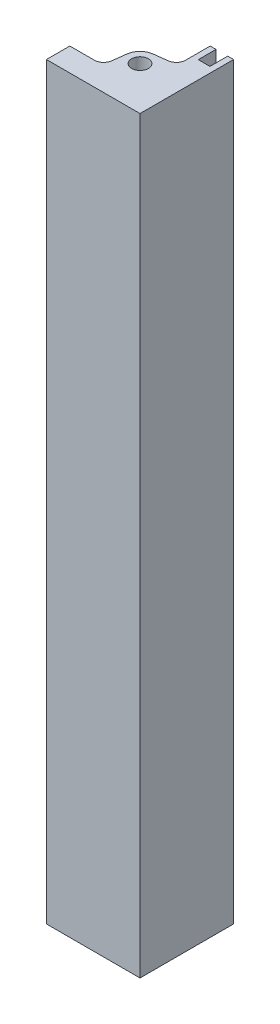
SolidWorks part; units mm, degrees
ref_plane "Front Plane" through (0, 0, 0) normal (0, 0, 1) x (1, 0, 0)
ref_plane "Top Plane" through (0, 0, 0) normal (0, 1, 0) x (1, 0, 0)
ref_plane "Right Plane" through (0, 0, 0) normal (1, 0, 0) x (0, 0, -1)
sketch "Sketch1" plane through (0, 0, 0) normal (0, 1, 0) x (1, 0, 0)
  line L0 (0, 0) -> (25.4, 0)
  line L1 (25.4, 0) -> (25.4, 25.4)
  line L2 (25.4, 25.4) -> (19.05, 25.4)
  line L3 (19.05, 25.4) -> (19.05, 6.35)
  line L4 (19.05, 6.35) -> (0, 6.35)
  line L5 (0, 6.35) -> (0, 0)
  dimension "D1" = 25.4
  dimension "D2" = 6.35
extrude "Boss-Extrude1" add sketch "Sketch1" along normal blind 203.2
sketch "Sketch2" plane through (0, 203.2, 0) normal (0, 1, 0) x (1, 0, 0)
  line L0 (19.05, 25.4) -> (19.05, 6.35) construction
  line L1 (19.05, 6.35) -> (0, 6.35) construction
  line L2 (19.05, 16.51) -> (19.05, 6.35)
  line L3 (19.05, 6.35) -> (8.89, 6.35)
  line L4 (8.89, 6.35) -> (9.6295, 12.244)
  line L5 (19.05, 16.51) -> (13.156, 15.7705)
  line L6 (13.6618, 11.7382) -> (19.05, 6.35) construction
  arc A0 (13.156, 15.7705) -> (9.6295, 12.244) centre (13.6618, 11.7382) ccw
  circle A1 centre (13.6618, 11.7382) radius 2.286
  dimension "D4" = 4.572
  dimension "D5" = 1.778
  dimension "D1" = 45
  dimension "D2" = 10.16
  dimension "D3" = 10.16
  dimension "D6" = 7.62
extrude "Boss-Extrude2" add sketch "Sketch2" against normal blind 6.35
ref_plane "Plane1" through (0, 101.6, 0) normal (0, 1, 0) x (1, 0, 0)
fillet "Fillet1" radius 2.54 2 edges at (19.05, 200.025, -16.51) (8.89, 200.025, -6.35)
mirror "Mirror1" about plane through (0, 101.6, 0) normal (0, 1, 0) of "Fillet1", "Boss-Extrude2"
sketch "Sketch4" plane through (0, 0, 0) normal (0, -1, 0) x (1, 0, 0)
  line L0 (25.4, -25.4) -> (19.05, -25.4) construction
  line L1 (20.6375, -25.4) -> (23.8125, -25.4)
  line L2 (20.6375, -25.4) -> (20.6375, -20.574)
  line L3 (20.6375, -20.574) -> (23.8125, -20.574)
  line L4 (23.8125, -25.4) -> (23.8125, -20.574)
  point P6 (22.225, -25.4)
  point P7 (22.225, -25.4)
  dimension "D1" = 3.175
  dimension "D2" = 4.826
extrude "Cut-Extrude2" cut sketch "Sketch4" against normal through all
sketch "Sketch5" plane through (19.05, 0, 0) normal (-1, 0, 0) x (0, 0, 1)
  line L0 (-25.4, 203.2) -> (-25.4, 0) construction
  line L1 (-25.4, 190.5) -> (-6.35, 190.5)
  line L2 (-25.4, 190.5) -> (-25.4, 185.674)
  line L3 (-25.4, 185.674) -> (-6.35, 185.674)
  line L4 (-6.35, 190.5) -> (-6.35, 185.674)
  line L5 (-6.35, 196.85) -> (-6.35, 6.35) construction
  line L6 (-18.7512, 196.85) -> (-16.231, 196.85) construction
  line L7 (-25.4, 180.8903) -> (-25.4, 176.0643)
  line L8 (-25.4, 180.8903) -> (-6.35, 180.8903)
  line L9 (-6.35, 180.8903) -> (-6.35, 176.0643)
  line L10 (-25.4, 176.0643) -> (-6.35, 176.0643)
  line L11 (-25.4, 171.2807) -> (-25.4, 166.4547)
  line L12 (-25.4, 171.2807) -> (-6.35, 171.2807)
  line L13 (-6.35, 171.2807) -> (-6.35, 166.4547)
  line L14 (-25.4, 166.4547) -> (-6.35, 166.4547)
  line L15 (-25.4, 161.671) -> (-25.4, 156.845)
  line L16 (-25.4, 161.671) -> (-6.35, 161.671)
  line L17 (-6.35, 161.671) -> (-6.35, 156.845)
  line L18 (-25.4, 156.845) -> (-6.35, 156.845)
  line L19 (-25.4, 152.0613) -> (-25.4, 147.2353)
  line L20 (-25.4, 152.0613) -> (-6.35, 152.0613)
  line L21 (-6.35, 152.0613) -> (-6.35, 147.2353)
  line L22 (-25.4, 147.2353) -> (-6.35, 147.2353)
  line L23 (-25.4, 142.4517) -> (-25.4, 137.6257)
  line L24 (-25.4, 142.4517) -> (-6.35, 142.4517)
  line L25 (-6.35, 142.4517) -> (-6.35, 137.6257)
  line L26 (-25.4, 137.6257) -> (-6.35, 137.6257)
  line L27 (-25.4, 132.842) -> (-25.4, 128.016)
  line L28 (-25.4, 132.842) -> (-6.35, 132.842)
  line L29 (-6.35, 132.842) -> (-6.35, 128.016)
  line L30 (-25.4, 128.016) -> (-6.35, 128.016)
  line L31 (-25.4, 123.2323) -> (-25.4, 118.4063)
  line L32 (-25.4, 123.2323) -> (-6.35, 123.2323)
  line L33 (-6.35, 123.2323) -> (-6.35, 118.4063)
  line L34 (-25.4, 118.4063) -> (-6.35, 118.4063)
  line L35 (-25.4, 113.6227) -> (-25.4, 108.7967)
  line L36 (-25.4, 113.6227) -> (-6.35, 113.6227)
  line L37 (-6.35, 113.6227) -> (-6.35, 108.7967)
  line L38 (-25.4, 108.7967) -> (-6.35, 108.7967)
  line L39 (-25.4, 104.013) -> (-25.4, 99.187)
  line L40 (-25.4, 104.013) -> (-6.35, 104.013)
  line L41 (-6.35, 104.013) -> (-6.35, 99.187)
  line L42 (-25.4, 99.187) -> (-6.35, 99.187)
  line L43 (-25.4, 94.4033) -> (-25.4, 89.5773)
  line L44 (-25.4, 94.4033) -> (-6.35, 94.4033)
  line L45 (-6.35, 94.4033) -> (-6.35, 89.5773)
  line L46 (-25.4, 89.5773) -> (-6.35, 89.5773)
  line L47 (-25.4, 84.7937) -> (-25.4, 79.9677)
  line L48 (-25.4, 84.7937) -> (-6.35, 84.7937)
  line L49 (-6.35, 84.7937) -> (-6.35, 79.9677)
  line L50 (-25.4, 79.9677) -> (-6.35, 79.9677)
  line L51 (-25.4, 75.184) -> (-25.4, 70.358)
  line L52 (-25.4, 75.184) -> (-6.35, 75.184)
  line L53 (-6.35, 75.184) -> (-6.35, 70.358)
  line L54 (-25.4, 70.358) -> (-6.35, 70.358)
  line L55 (-25.4, 65.5743) -> (-25.4, 60.7483)
  line L56 (-25.4, 65.5743) -> (-6.35, 65.5743)
  line L57 (-6.35, 65.5743) -> (-6.35, 60.7483)
  line L58 (-25.4, 60.7483) -> (-6.35, 60.7483)
  line L59 (-25.4, 55.9647) -> (-25.4, 51.1387)
  line L60 (-25.4, 55.9647) -> (-6.35, 55.9647)
  line L61 (-6.35, 55.9647) -> (-6.35, 51.1387)
  line L62 (-25.4, 51.1387) -> (-6.35, 51.1387)
  line L63 (-25.4, 46.355) -> (-25.4, 41.529)
  line L64 (-25.4, 46.355) -> (-6.35, 46.355)
  line L65 (-6.35, 46.355) -> (-6.35, 41.529)
  line L66 (-25.4, 41.529) -> (-6.35, 41.529)
  line L67 (-25.4, 36.7453) -> (-25.4, 31.9193)
  line L68 (-25.4, 36.7453) -> (-6.35, 36.7453)
  line L69 (-6.35, 36.7453) -> (-6.35, 31.9193)
  line L70 (-25.4, 31.9193) -> (-6.35, 31.9193)
  line L71 (-25.4, 27.1357) -> (-25.4, 22.3097)
  line L72 (-25.4, 27.1357) -> (-6.35, 27.1357)
  line L73 (-6.35, 27.1357) -> (-6.35, 22.3097)
  line L74 (-25.4, 22.3097) -> (-6.35, 22.3097)
  line L75 (-25.4, 17.526) -> (-25.4, 12.7)
  line L76 (-25.4, 17.526) -> (-6.35, 17.526)
  line L77 (-6.35, 17.526) -> (-6.35, 12.7)
  line L78 (-25.4, 12.7) -> (-6.35, 12.7)
  line L79 (-16.231, 6.35) -> (-18.7512, 6.35) construction
  dimension "D1" = 4.826
  dimension "D2" = 6.35
  dimension "D4" = 6.35
  dimension "D3" = 19
extrude "Boss-Extrude3" add sketch "Sketch5" along normal blind 6.35
